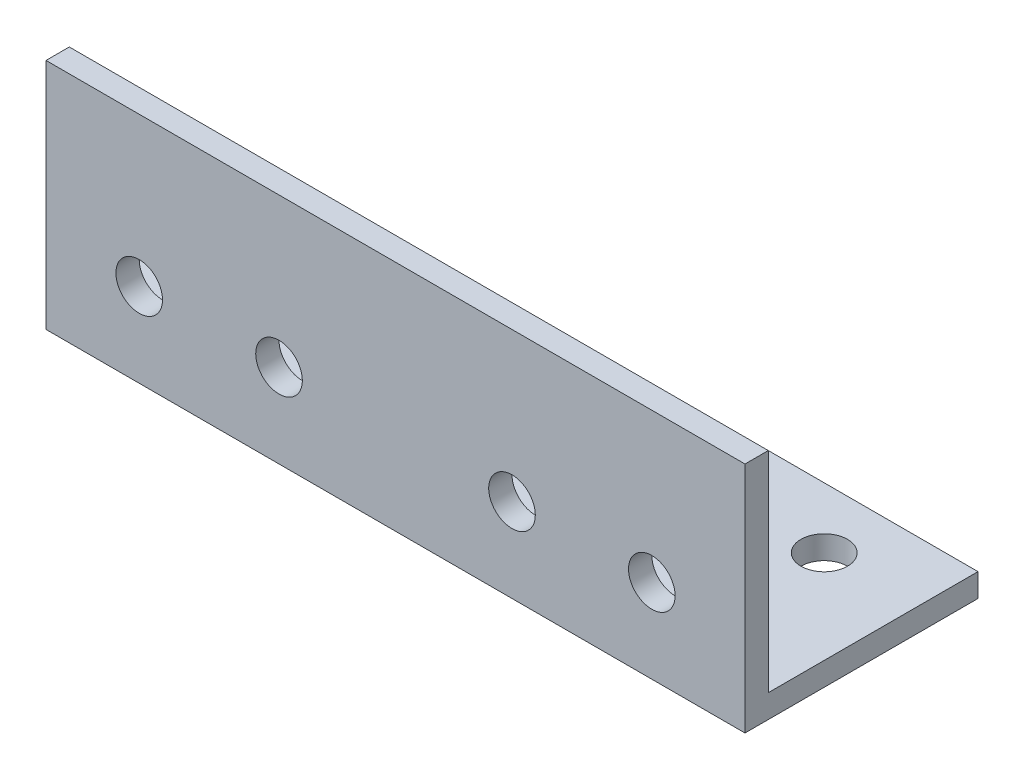
SolidWorks part; units mm, degrees
ref_plane "Спереди" through (0, 0, 0) normal (0, 0, 1) x (1, 0, 0)
ref_plane "Сверху" through (0, 0, 0) normal (0, 1, 0) x (1, 0, 0)
ref_plane "Справа" through (0, 0, 0) normal (1, 0, 0) x (0, 0, -1)
sketch "Эскиз1" plane through (0, 0, 0) normal (1, 0, 0) x (0, 0, -1)
  line L0 (0, 0) -> (0, 50)
  line L1 (0, 0) -> (50, 0)
extrude "Вытянуть-Тонкостенный1" add sketch "Эскиз1" along normal blind 150 thin thin type one direction reverse wall 5
sketch "Эскиз2" plane through (0, 0, 0) normal (0, -1, 0) x (1, 0, 0)
  line L0 (75, -58.7293) -> (75, -21.2393) construction
  circle A0 centre (130, -37) radius 5
  circle A1 centre (100, -37) radius 5
  circle A2 centre (50, -37) radius 5
  circle A3 centre (20, -37) radius 5
  dimension "D1" = 2
extrude "Вырез-Вытянуть1" cut sketch "Эскиз2" against normal through all
sketch "Эскиз3" plane through (0, 0, 0) normal (0, 0, 1) x (1, 0, 0)
  line L0 (75, 50) -> (75, 0) construction
  line L1 (150, 50) -> (0, 50) construction
  circle A0 centre (130, 18) radius 5
  circle A1 centre (100, 18) radius 5
  circle A2 centre (50, 18) radius 5
  circle A3 centre (20, 18) radius 5
  dimension "D1" = 2
extrude "Вырез-Вытянуть3" cut sketch "Эскиз3" against normal through all
